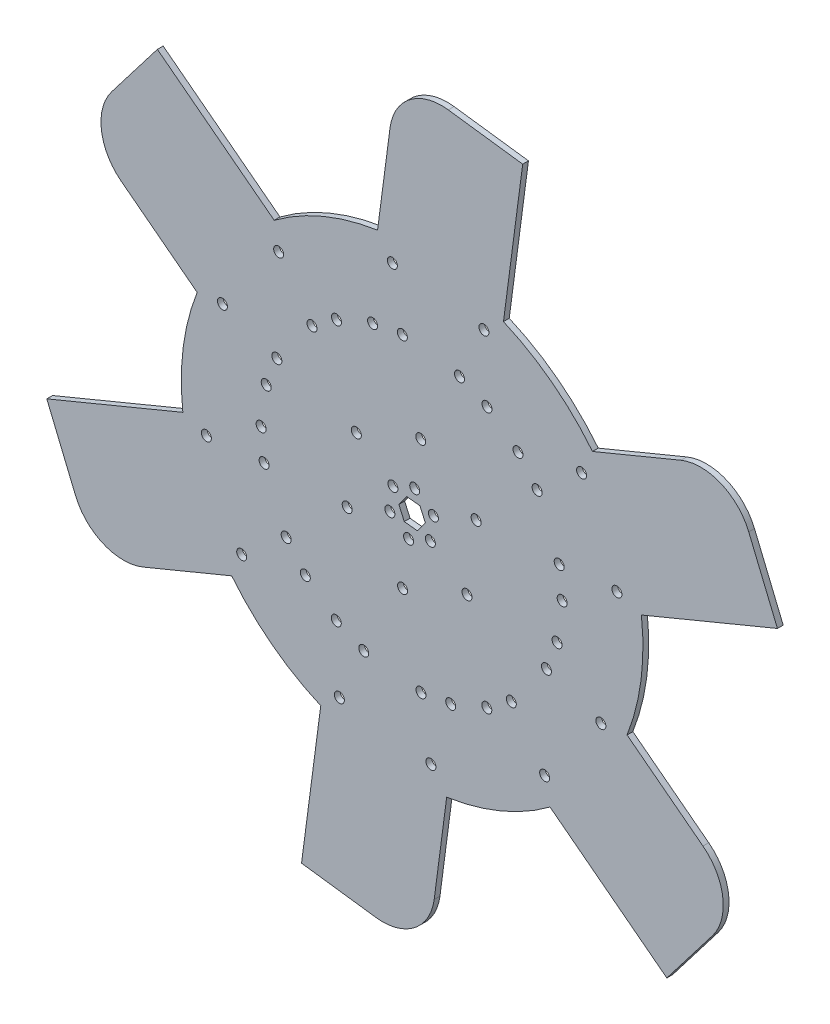
SolidWorks part; units mm, degrees
note: '?' marks a value the reader was unsure of.
ref_plane "Front Plane" through (0, 0, 0) normal (0, 0, 1) x (1, 0, 0)
ref_plane "Top Plane" through (0, 0, 0) normal (0, 1, 0) x (1, 0, 0)
ref_plane "Right Plane" through (0, 0, 0) normal (1, 0, 0) x (0, 0, -1)
sketch "Sketch1" plane through (0, 0, 0) normal (0, 0, 1) x (1, 0, 0)
  circle A0 centre (0, 0) radius 127
  dimension "D1" = 254
extrude "Boss-Extrude1" add sketch "Sketch1" along normal blind 3.175
sketch "Sketch2" plane through (0, 0, 0) normal (0, 0, 1) x (1, 0, 0)
  line L0 (0, 0) -> (117.3327, 48.6008) construction
  circle A0 centre (0, 0) radius 82.55 construction
  circle A1 centre (0, 0) radius 114.3 construction
  point P0 (11.7333, 4.8601)
  point P3 (80.9178, 16.3343)
  point P5 (58.2494, 58.4937)
  point P6 (82.5498, -0.1727)
  point P7 (112.6792, 19.1805)
  point P8 (93.2389, 66.1136)
  point P10 (68.7676, 45.6675)
  point P11 (35.1998, 14.5802)
  dimension "D1" = 12.7
  dimension "D3" = 165.1
  dimension "D4" = 228.6
  dimension "D6" = 31.75
  dimension "D2" = 63.5
  dimension "D5" = 50.8
  dimension "D7" = 38.1
hole_wizard "M5 Clearance Hole1" positions "Sketch3" profile "Sketch4" hole size "M5" standard "ANSI Metric" end condition through all
sketch "Sketch3" plane through (0, 0, 0) normal (0, 0, -1) x (-1, 0, 0)
  point P0 (-58.2494, 58.4937)
  point P3 (-82.5498, -0.1727)
  point P6 (-93.2389, 66.1136)
  point P9 (-112.6792, 19.1805)
  point P12 (-11.7333, 4.8601)
  point P16 (-68.7676, 45.6675)
  point P19 (-80.9178, 16.3343)
  point P22 (-35.1998, 14.5802)
sketch "Sketch4" plane through (58.2494, 58.4937, 0) normal (1, 0, 0) x (0, 1, 0)
  line L0 (0, 0) -> (0, 3.175)
  line L1 (0, 3.175) -> (2.75, 3.175)
  line L2 (2.75, 3.175) -> (2.75, 0)
  line L5 (2.75, 0) -> (0, 0)
  line L11 (0, -6.35) -> (0, 107.95) construction
  dimension "Thru Hole Dia." = 5.5
  dimension "Thru Hole Depth" = 3.175
ref_axis "Axis1" through (0, 0, -0.1588) along (0, 0, 1)?
pattern_circular "CirPattern1" count 6 over 360 about axis through (-0.2557, -0.1059, 0) along (0, 0, 1) of "M5 Clearance Hole1"
sketch "Sketch6" plane through (0, 0, 0) normal (0, 0, -1) x (-1, 0, 0)
  line L1 (-97.9793, 78.7306) -> (-147.8457, 99.3859)
  line L2 (-185.1808, 83.9212) -> (-200.976, 45.7881)
  line L3 (-200.976, 45.7881) -> (-124.7098, 14.1976)
  line L4 (-124.7098, 14.1976) -> (-97.9793, 78.7306)
  line L5 (0, 0) -> (-117.3327, 48.6008) construction
  arc A0 (-185.1808, 83.9212) -> (-147.8457, 99.3859) centre (-158.7809, 72.9861) cw
  dimension "D5" = 28.575
  dimension "D1" = 69.85
  dimension "8" = 203.2
  dimension "D4" = 35.2425
extrude "Boss-Extrude2" add sketch "Sketch6" against normal up to surface (3.175 mm away) up to face at (39.8299, 69.1908, 3.175)
pattern_circular "CirPattern2" count 6 over 360 about axis through (0, 0, 0) along (0, 0, 1) of "Boss-Extrude2"
sketch "Sketch7" plane through (0, 0, 3.175) normal (0, 0, 1) x (1, 0, 0)
  line L1 (7.2922, -0.7664) -> (4.3098, 5.932)
  line L2 (4.3098, 5.932) -> (-2.9823, 6.6984)
  line L3 (-2.9823, 6.6984) -> (-7.2922, 0.7664)
  line L4 (-7.2922, 0.7664) -> (-4.3098, -5.932)
  line L5 (-4.3098, -5.932) -> (2.9823, -6.6984)
  line L6 (2.9823, -6.6984) -> (7.2922, -0.7664)
  circle A0 centre (0, 0) radius 6.35 construction
extrude "Cut-Extrude1" cut sketch "Sketch7" against normal through all
